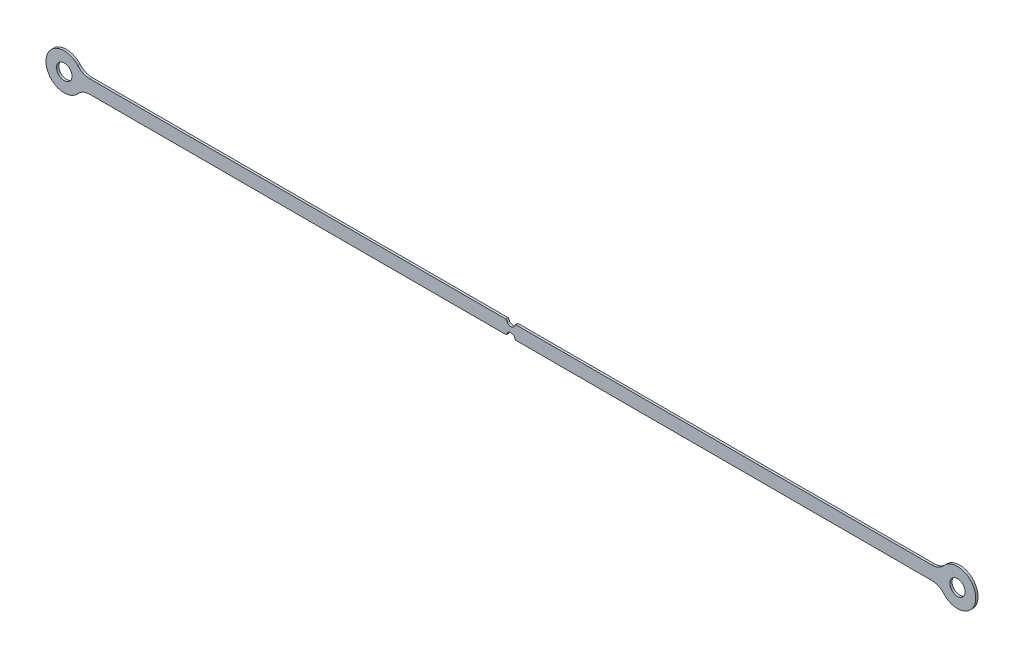
SolidWorks part; units mm, degrees
ref_plane "Front Plane" through (0, 0, 0) normal (0, 0, 1) x (1, 0, 0)
ref_plane "Top Plane" through (0, 0, 0) normal (0, 1, 0) x (1, 0, 0)
ref_plane "Right Plane" through (0, 0, 0) normal (1, 0, 0) x (0, 0, -1)
sketch "Sketch1" plane through (0, 0, 0) normal (0, 0, 1) x (1, 0, 0)
  line L0 (0, -0.5623) -> (0, -10.0623) construction
  line L7 (0, 1.35) -> (0, -1.35)
  line L10 (232, 0) -> (-232, 0) construction
  line L11 (2.6024, 3.5) -> (218.8091, 3.5)
  line L12 (2.6024, -3.5) -> (218.8091, -3.5)
  line L13 (-2.6024, -3.5) -> (-218.8091, -3.5)
  line L14 (-2.6024, 3.5) -> (-218.8091, 3.5)
  arc A0 (224.8392, -6.2429) -> (224.8392, 6.2429) centre (232, 0) ccw
  circle A1 centre (232, 0) radius 4
  arc A6 (-2.1114, 3.0943) -> (2.1114, 3.0943) centre (0, 3.5) ccw
  arc A7 (-2.1114, -3.0943) -> (2.1114, -3.0943) centre (0, -3.5) cw
  arc A8 (224.8392, 6.2429) -> (218.8091, 3.5) centre (218.8091, 11.5) cw
  arc A9 (224.8392, -6.2429) -> (218.8091, -3.5) centre (218.8091, -11.5) ccw
  arc A10 (2.6024, 3.5) -> (2.1114, 3.0943) centre (2.6024, 3) ccw
  arc A11 (2.6024, -3.5) -> (2.1114, -3.0943) centre (2.6024, -3) cw
  arc A12 (-2.6024, -3.5) -> (-2.1114, -3.0943) centre (-2.6024, -3) ccw
  arc A13 (-2.6024, 3.5) -> (-2.1114, 3.0943) centre (-2.6024, 3) cw
  arc A14 (-224.8392, -6.2429) -> (-218.8091, -3.5) centre (-218.8091, -11.5) cw
  arc A15 (-224.8392, 6.2429) -> (-218.8091, 3.5) centre (-218.8091, 11.5) ccw
  circle A16 centre (-232, 0) radius 4
  arc A17 (-224.8392, -6.2429) -> (-224.8392, 6.2429) centre (-232, 0) cw
  point P0 (0, 0)
  point P11 (213.5949, 3.3201)
  point P14 (213.865, 3.3089)
  point P19 (223.1682, 3.5)
  point P22 (223.1682, -3.5)
  point P25 (2.15, 3.5)
  point P28 (2.15, -3.5)
  point P30 (0, 0)
  point P43 (-2.15, -3.5)
  point P44 (-2.15, 3.5)
  point P45 (-223.1682, -3.5)
  point P46 (-223.1682, 3.5)
  dimension "D2" = 9.5
  dimension "D4" = 8
  dimension "D5" = 3.5
  dimension "D6" = 7
  dimension "D7" = 8
  dimension "D8" = 8
  dimension "D9" = 0.5
  dimension "D10" = 0.5
  dimension "D1" = 232
extrude "Boss-Extrude1" add sketch "Sketch1" along normal blind 1.2 contours L0 L7 | L0 L7 A0 A1 region at (127.843, 0, 0) region at (-127.843, 0, 0)
